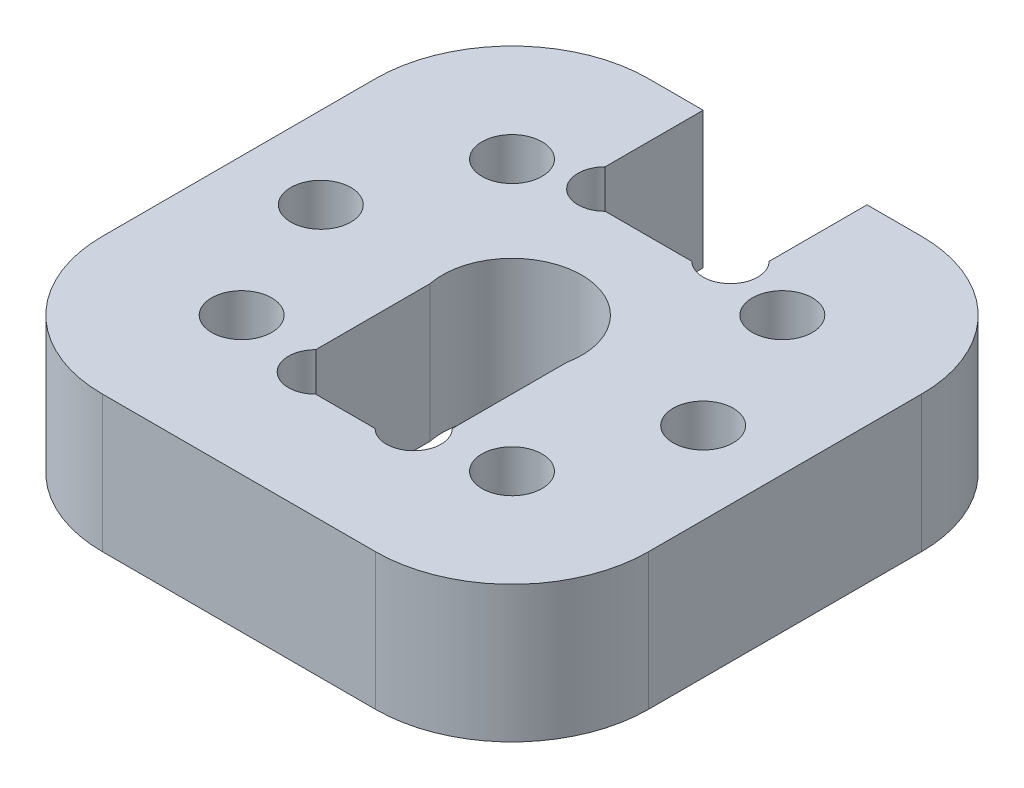
SolidWorks part; units mm, degrees
ref_plane "정면" through (0, 0, 0) normal (0, 0, 1) x (1, 0, 0)
ref_plane "윗면" through (0, 0, 0) normal (0, 1, 0) x (1, 0, 0)
ref_plane "우측면" through (0, 0, 0) normal (1, 0, 0) x (0, 0, -1)
sketch "스케치1" plane through (0, 0, 0) normal (0, 1, 0) x (1, 0, 0)
  line L1 (-10, -10) -> (10, -10)
  line L2 (-10, -10) -> (-10, 10)
  line L3 (-10, 10) -> (10, 10)
  line L4 (10, -10) -> (10, 10)
  line L5 (-10, -10) -> (10, 10) construction
  line L6 (-10, 10) -> (10, -10) construction
  point P0 (0, 0)
  dimension "D1" = 20
extrude "보스-돌출1" add sketch "스케치1" along normal blind 5
sketch "스케치2" plane through (0, 5, 0) normal (0, 1, 0) x (1, 0, 0)
  circle A0 centre (0, 0) radius 2.55
  dimension "D1" = 5.1
extrude "컷-돌출1" cut sketch "스케치2" against normal blind 5
sketch "스케치3" plane through (0, 0, 0) normal (0, -1, 0) x (1, 0, 0)
  line L0 (2.5, 6.1) -> (2.5, 2.5) construction
  line L1 (-2.5, 6.1) -> (2.5, 6.1)
  line L2 (-2.5, 6.1) -> (-2.5, 0)
  line L3 (-2.5, 0) -> (2.5, 0)
  line L4 (2.5, 6.1) -> (2.5, 0)
extrude "컷-돌출2" cut sketch "스케치3" against normal blind 5
sketch "스케치4" plane through (0, 0, 0) normal (0, -1, 0) x (1, 0, 0)
  line L0 (2.5, 6.1) -> (1.7929, 5.3929) construction
  line L1 (-2.5, 6.1) -> (-1.7929, 5.3929) construction
  line L2 (2.5, 6.1) -> (-2.5, 6.1) construction
  circle A0 centre (1.7929, 5.3929) radius 1
  circle A1 centre (-1.7929, 5.3929) radius 1
  dimension "D3" = 2
  dimension "D1" = 45
  dimension "D2" = 45
sketch "스케치5" plane through (0, 0, 0) normal (0, -1, 0) x (-1, 0, 0)
  line L0 (-2.5, -6.1) -> (-1.7929, -5.3929) construction
  line L1 (2.5, -6.1) -> (1.7929, -5.3929) construction
  line L2 (-2.5, -6.1) -> (2.5, -6.1) construction
  circle A0 centre (-1.7929, -5.3929) radius 1
  circle A1 centre (1.7929, -5.3929) radius 1
  dimension "D3" = 2
  dimension "D1" = 45
  dimension "D2" = 45
extrude "컷-돌출4" cut sketch "스케치5" against normal blind 10
fillet "필렛1" radius 5 4 edges at (10, 2.5, -10) (-10, 2.5, -10) (-10, 2.5, 10) (10, 2.5, 10)
extrude "컷-돌출3" [suppressed] cut sketch "스케치4" against normal blind 5
sketch "스케치6" plane through (0, 0, 0) normal (0, -1, 0) x (1, 0, 0)
  line L0 (5, -10) -> (-5, -10) construction
  line L1 (-3, -5) -> (3, -5)
  line L2 (-3, -5) -> (-3, -10)
  line L3 (-3, -10) -> (3, -10)
  line L4 (3, -5) -> (3, -10)
  dimension "D1" = 5
extrude "컷-돌출5" cut sketch "스케치6" against normal blind 10
sketch "스케치7" plane through (0, 0, 0) normal (0, -1, 0) x (-1, 0, 0)
  line L0 (-3, 5) -> (-2.2929, 5.7071) construction
  line L1 (3, 5) -> (2.2929, 5.7071) construction
  line L2 (-3, 5) -> (3, 5) construction
  circle A0 centre (-2.2929, 5.7071) radius 1
  circle A1 centre (2.2929, 5.7071) radius 1
  dimension "D3" = 2
  dimension "D1" = 45
  dimension "D2" = 45
extrude "컷-돌출6" cut sketch "스케치7" against normal blind 10
sketch "스케치8" plane through (0, 0, 0) normal (0, -1, 0) x (1, 0, 0)
  line L0 (4.9497, 4.9497) -> (0, 0) construction
  line L1 (0, 0) -> (0, 7) construction
  circle A0 centre (0, 0) radius 7 construction
  circle A1 centre (4.9497, 4.9497) radius 1.1
  circle A2 centre (7, 0) radius 1.1
  circle A3 centre (4.9497, -4.9497) radius 1.1
  circle A5 centre (-4.9497, -4.9497) radius 1.1
  circle A6 centre (-7, 0) radius 1.1
  circle A7 centre (-4.9497, 4.9497) radius 1.1
  circle A9 centre (0, 7) radius 1.1 [skipped]
  circle A10 centre (0, -7) radius 1.1 [skipped]
  point P23 (0, 0)
  dimension "D1" = 2.2
  dimension "D2" = 45
  dimension "D3" = 8
extrude "컷-돌출7" cut sketch "스케치8" against normal blind 5
